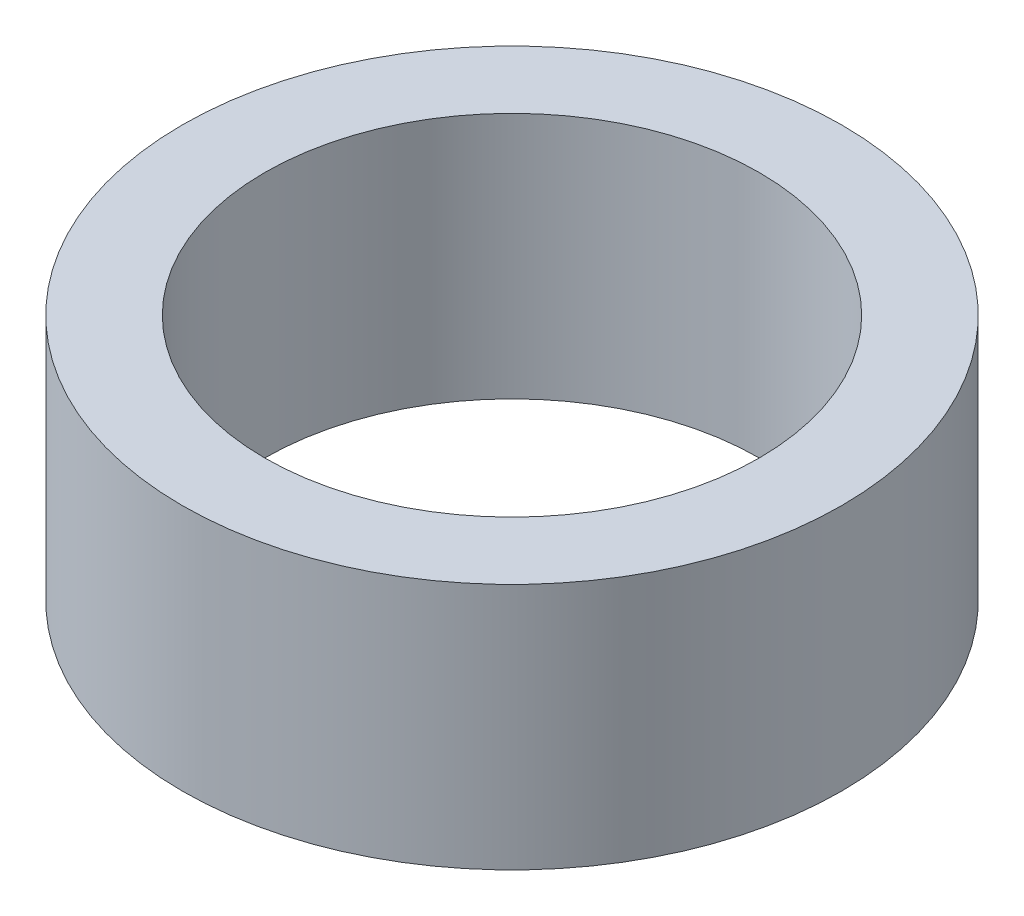
SolidWorks part; units mm, degrees
ref_plane "Front Plane" through (0, 0, 0) normal (0, 0, 1) x (1, 0, 0)
ref_plane "Top Plane" through (0, 0, 0) normal (0, 1, 0) x (1, 0, 0)
ref_plane "Right Plane" through (0, 0, 0) normal (1, 0, 0) x (0, 0, -1)
sketch "Sketch1" plane through (0, 0, 0) normal (0, 1, 0) x (1, 0, 0)
  circle A0 centre (0, 0) radius 6.35
  circle A1 centre (0, 0) radius 4.7625
  dimension "D1" = 9.525
  dimension "D2" = 12.7
extrude "Boss-Extrude1" add sketch "Sketch1" along normal blind 4.7625 contours A1 | A0 region at (0, 0, 0)
